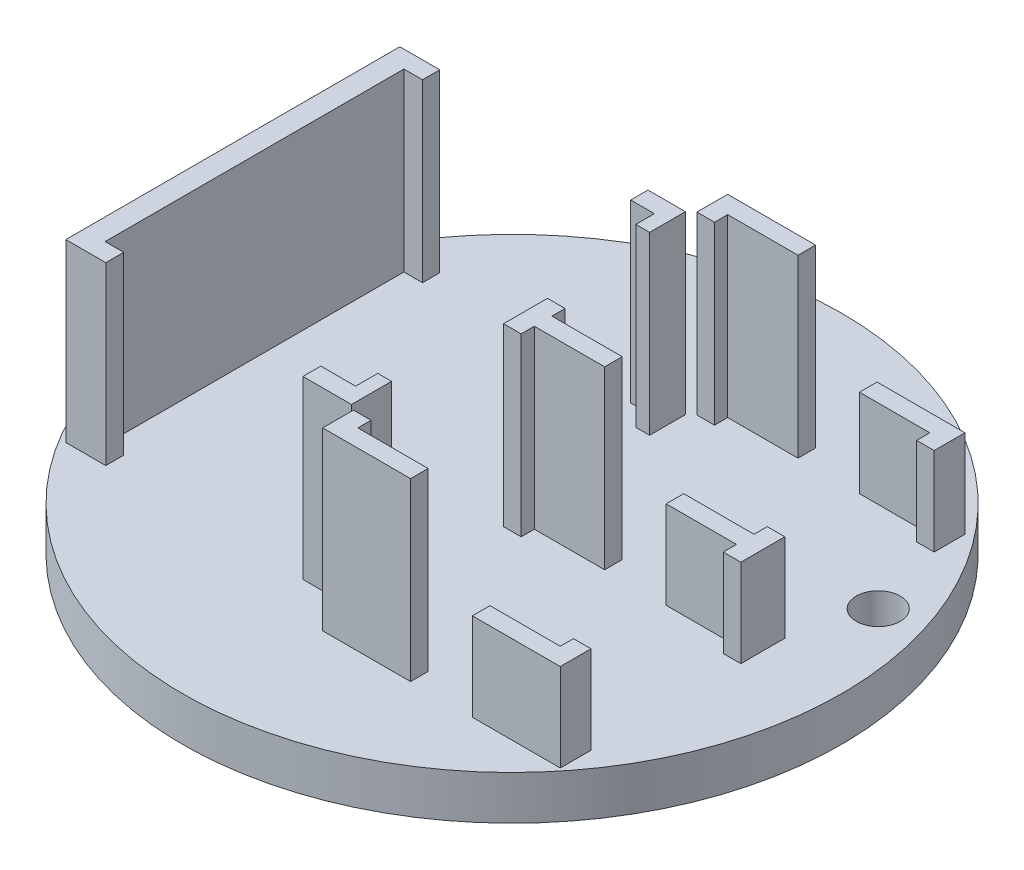
SolidWorks part; units mm, degrees
ref_plane "Ebene vorne" through (0, 0, 0) normal (0, 0, 1) x (1, 0, 0)
ref_plane "Ebene oben" through (0, 0, 0) normal (0, 1, 0) x (1, 0, 0)
ref_plane "Ebene rechts" through (0, 0, 0) normal (1, 0, 0) x (0, 0, -1)
sketch "Skizze1" plane through (0, 0, 0) normal (0, 1, 0) x (1, 0, 0)
  line L0 (0, 0) -> (0, -75)
  line L1 (0, -37.5) -> (-48.465, -37.5) construction
  arc A1 (0, -75) -> (0, 0) centre (0, -37.5) cw
  dimension "D1" = 75
extrude "Aufsatz-Linear austragen1" add sketch "Skizze1" along normal blind 5
sketch "Skizze15" plane through (0, 5, 0) normal (0, 1, 0) x (1, 0, 0)
  line L0 (-4.6482, -31.3911) -> (-13.6482, -31.3911) construction
  line L1 (1.8063, -35.2746) -> (3.8063, -35.2746)
  line L2 (3.8063, -36.7746) -> (3.8063, -35.2746)
  line L3 (3.8063, -36.7746) -> (11.8063, -36.7746)
  line L4 (26.8063, -36.7746) -> (26.8063, -35.2746)
  line L5 (3.8063, -16.7746) -> (11.8063, -16.7746)
  line L6 (1.8063, -38.7746) -> (1.8063, -35.2746)
  line L8 (28.8063, -38.7746) -> (28.8063, -35.2746)
  line L9 (1.8063, -14.7746) -> (11.8063, -14.7746)
  line L10 (11.8063, -36.7746) -> (11.8063, -38.7746)
  line L11 (18.8063, -36.7746) -> (18.8063, -38.7746)
  line L13 (18.8063, -36.7746) -> (26.8063, -36.7746)
  line L14 (1.8063, -18.2746) -> (3.8063, -18.2746)
  line L15 (11.8063, -16.7746) -> (11.8063, -14.7746)
  line L16 (18.8063, -16.7746) -> (18.8063, -14.7746)
  line L17 (26.8063, -18.2746) -> (28.8063, -18.2746)
  line L18 (26.8063, -35.2746) -> (28.8063, -35.2746)
  line L19 (18.8063, -16.7746) -> (26.8063, -16.7746)
  line L20 (18.8063, -14.7746) -> (28.8063, -14.7746)
  line L21 (28.8063, -18.2746) -> (28.8063, -14.7746)
  line L22 (26.8063, -18.2746) -> (26.8063, -16.7746)
  line L23 (1.8063, -18.2746) -> (1.8063, -14.7746)
  line L24 (3.8063, -18.2746) -> (3.8063, -16.7746)
  line L25 (3.8063, -38.7746) -> (3.8063, -40.2746)
  line L26 (3.8063, -40.2746) -> (1.8063, -40.2746)
  line L27 (1.8063, -40.2746) -> (1.8063, -38.7746)
  line L28 (3.8063, -38.7746) -> (11.8063, -38.7746)
  line L29 (26.8063, -38.7746) -> (26.8063, -40.2746)
  line L30 (26.8063, -40.2746) -> (28.8063, -40.2746)
  line L31 (28.8063, -40.2746) -> (28.8063, -38.7746)
  line L32 (26.8063, -38.7746) -> (18.8063, -38.7746)
sketch "Skizze19" plane through (0, 5, 0) normal (0, 1, 0) x (1, 0, 0)
  line L0 (0, -37.5) -> (-52.774, -37.5) construction
  line L1 (0, -75) -> (0, 0) construction
  line L2 (-28.9568, -75) -> (-28.9568, 0) construction
  line L3 (-0.4568, -20.8495) -> (-0.4568, -54.8495)
  line L4 (-0.4568, -20.8495) -> (-28.9568, -20.8495)
  line L5 (-28.9568, -20.8495) -> (-28.9568, -54.8495)
  line L6 (-28.9568, -54.8495) -> (-0.4568, -54.8495)
  line L7 (-31.3875, -18.8876) -> (1.1125, -18.8876)
  line L8 (-31.3875, -18.8876) -> (-31.3875, -56.8876)
  line L9 (-31.3875, -56.8876) -> (1.1125, -56.8876)
  line L10 (1.1125, -56.8876) -> (1.1125, -18.8876)
extrude "Aufsatz-Linear austragen2" add sketch "Skizze19" along normal blind 20
sketch "Skizze20" plane through (0, 5, 0) normal (0, 1, 0) x (1, 0, 0)
  line L0 (0, -75) -> (0, 0)
  arc A0 (0, 0) -> (0, -75) centre (0, -37.5) cw
extrude "Aufsatz-Linear austragen3" add sketch "Skizze20" against normal blind 5
sketch "Skizze21" plane through (0, 5, 0) normal (0, 1, 0) x (1, 0, 0)
  line L0 (-4.6751, -53.4408) -> (-13.6751, -53.4408) construction
  line L1 (1.7794, -57.3243) -> (3.7794, -57.3303)
  line L2 (3.7794, -58.8303) -> (3.7794, -57.3303)
  line L3 (3.7794, -58.8303) -> (11.7794, -58.8303)
  line L4 (26.8151, -58.8303) -> (26.8151, -57.3303)
  line L6 (1.7794, -60.8303) -> (1.7794, -57.3243)
  line L7 (1.7794, -60.8303) -> (11.7794, -60.8303)
  line L8 (28.8151, -60.8303) -> (28.8151, -57.3303)
  line L10 (11.7794, -58.8303) -> (11.7794, -60.8303)
  line L11 (18.8151, -58.8303) -> (18.8151, -60.8303)
  line L12 (18.8151, -60.8303) -> (28.8151, -60.8303)
  line L13 (18.8151, -58.8303) -> (26.8151, -58.8303)
  line L18 (26.8151, -57.3303) -> (28.8151, -57.3303)
extrude "Aufsatz-Linear austragen4" add sketch "Skizze21" along normal blind 20
extrude "Aufsatz-Linear austragen5" add sketch "Skizze15" along normal blind 20
sketch "Skizze22" plane through (0, 25, 0) normal (0, 1, 0) x (1, 0, 0)
  line L0 (-4.4095, -54.8495) -> (-26.8437, -54.8495)
  line L1 (-28.9568, -54.8495) -> (-0.4568, -54.8495) construction
  line L2 (-26.8437, -54.8495) -> (-26.8437, -56.8876)
  line L3 (-31.3875, -56.8876) -> (1.1125, -56.8876) construction
  line L4 (-26.8437, -56.8876) -> (-4.4095, -56.8876)
  line L5 (-4.4095, -56.8876) -> (-4.4095, -54.8495)
  line L6 (-0.4568, -52.3272) -> (1.1125, -52.3272)
  line L7 (-0.4568, -54.8495) -> (-0.4568, -20.8495) construction
  line L8 (1.1125, -56.8876) -> (1.1125, -18.8876) construction
  line L9 (1.1125, -52.3272) -> (1.1125, -22.9658)
  line L10 (1.1125, -22.9658) -> (-0.4568, -22.9658)
  line L11 (-0.4568, -22.9658) -> (-0.4568, -52.3272)
  line L12 (-3.1509, -20.8495) -> (-26.8437, -20.8495)
  line L13 (-0.4568, -20.8495) -> (-28.9568, -20.8495) construction
  line L14 (-26.8437, -20.8495) -> (-26.8437, -18.8876)
  line L15 (1.1125, -18.8876) -> (-31.3875, -18.8876) construction
  line L16 (-26.8437, -18.8876) -> (-3.1509, -18.8876)
  line L17 (-3.1509, -18.8876) -> (-3.1509, -20.8495)
extrude "Schnitt-Linear austragen1" cut sketch "Skizze22" against normal blind 20
sketch "Skizze23" plane through (0, 25, 0) normal (0, 1, 0) x (1, 0, 0)
  line L0 (18.8151, -58.8303) -> (26.8151, -58.8303)
  line L1 (26.8151, -58.8303) -> (26.8151, -57.3303)
  line L2 (26.8151, -57.3303) -> (28.8151, -57.3303)
  line L3 (28.8151, -57.3303) -> (28.8151, -60.8303)
  line L4 (28.8151, -60.8303) -> (18.8151, -60.8303)
  line L5 (18.8151, -60.8303) -> (18.8151, -58.8303)
  line L6 (28.8063, -40.2746) -> (26.8063, -40.2746)
  line L7 (26.8063, -40.2746) -> (26.8063, -38.7746)
  line L8 (26.8063, -38.7746) -> (18.8063, -38.7746)
  line L9 (18.8063, -38.7746) -> (18.8063, -36.7746)
  line L10 (18.8063, -36.7746) -> (26.8063, -36.7746)
  line L11 (26.8063, -36.7746) -> (26.8063, -35.2746)
  line L12 (26.8063, -35.2746) -> (28.8063, -35.2746)
  line L13 (28.8063, -35.2746) -> (28.8063, -40.2746)
  line L14 (28.8063, -18.2746) -> (26.8063, -18.2746)
  line L15 (26.8063, -18.2746) -> (26.8063, -16.7746)
  line L16 (26.8063, -16.7746) -> (18.8063, -16.7746)
  line L17 (18.8063, -16.7746) -> (18.8063, -14.7746)
  line L18 (18.8063, -14.7746) -> (28.8063, -14.7746)
  line L19 (28.8063, -14.7746) -> (28.8063, -18.2746)
extrude "Schnitt-Linear austragen2" cut sketch "Skizze23" against normal blind 10
sketch "Skizze24" plane through (0, 5, 0) normal (0, 1, 0) x (1, 0, 0)
  circle A0 centre (31.2048, -27.0406) radius 2.5
extrude "Schnitt-Linear austragen3" cut sketch "Skizze24" against normal blind 5
